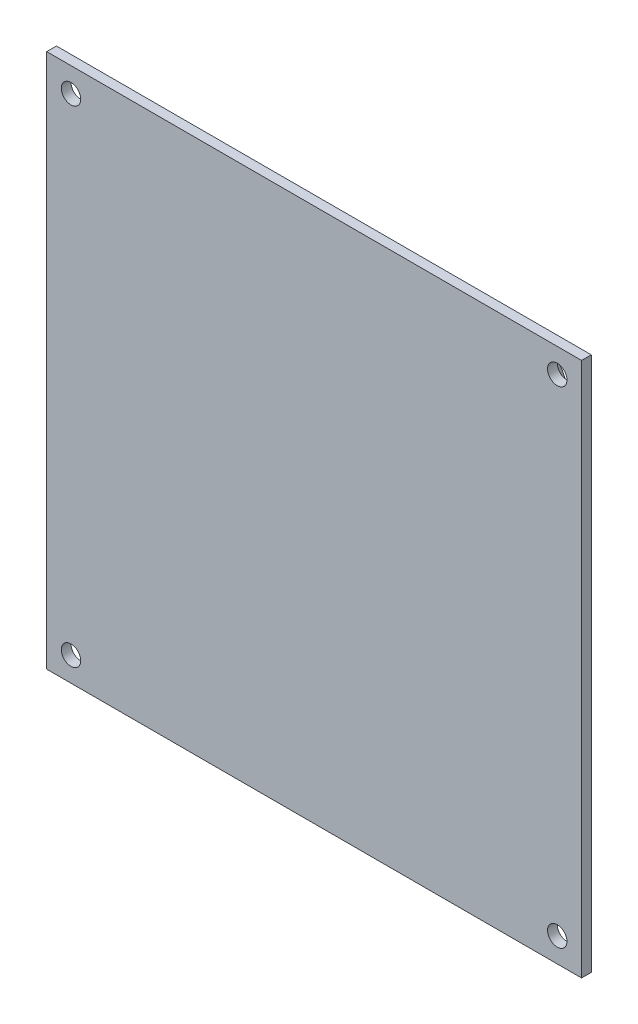
SolidWorks part; units mm, degrees
ref_plane "Front Plane" through (0, 0, 0) normal (0, 0, 1) x (1, 0, 0)
ref_plane "Top Plane" through (0, 0, 0) normal (0, 1, 0) x (1, 0, 0)
ref_plane "Right Plane" through (0, 0, 0) normal (1, 0, 0) x (0, 0, -1)
sketch "Sketch1" plane through (0, 0, 0) normal (0, 0, 1) x (1, 0, 0)
  line L1 (-55, 55) -> (55, 55)
  line L2 (-55, 55) -> (-55, -55)
  line L3 (-55, -55) -> (55, -55)
  line L4 (55, 55) -> (55, -55)
  line L5 (-55, 55) -> (55, -55) construction
  line L6 (-55, -55) -> (55, 55) construction
  line L7 (-50, 50) -> (50, 50) construction
  line L8 (-50, 50) -> (-50, -50) construction
  line L9 (-50, -50) -> (50, -50) construction
  line L10 (50, 50) -> (50, -50) construction
  line L11 (-50, 50) -> (50, -50) construction
  line L12 (-50, -50) -> (50, 50) construction
  circle A0 centre (-50, 50) radius 2
  circle A1 centre (-50, -50) radius 2
  circle A2 centre (50, -50) radius 2
  circle A3 centre (50, 50) radius 2
  point P0 (0, 0)
  point P6 (0, 0)
  dimension "D5" = 4
  dimension "D6" = 4
  dimension "D7" = 4
  dimension "D8" = 4
  dimension "D1" = 110
  dimension "D2" = 110
  dimension "D3" = 100
  dimension "D4" = 100
extrude "Boss-Extrude1" add sketch "Sketch1" along normal blind 2
sketch "Sketch3" plane through (0, 0, 0) normal (0, 0, -1) x (-1, 0, 0)
  line L1 (-5, 15) -> (5, 15)
  line L2 (-5, 15) -> (-5, -15)
  line L3 (-5, -15) -> (5, -15)
  line L4 (5, 15) -> (5, -15)
  line L5 (-5, 15) -> (5, -15) construction
  line L6 (-5, -15) -> (5, 15) construction
  point P0 (0, 0)
  dimension "D1" = 10
  dimension "D2" = 30
extrude "Boss-Extrude2" add sketch "Sketch3" along normal blind 45
fillet "Fillet1" radius 15 2 edges at (0, -15, -45) (0, 15, -45)
